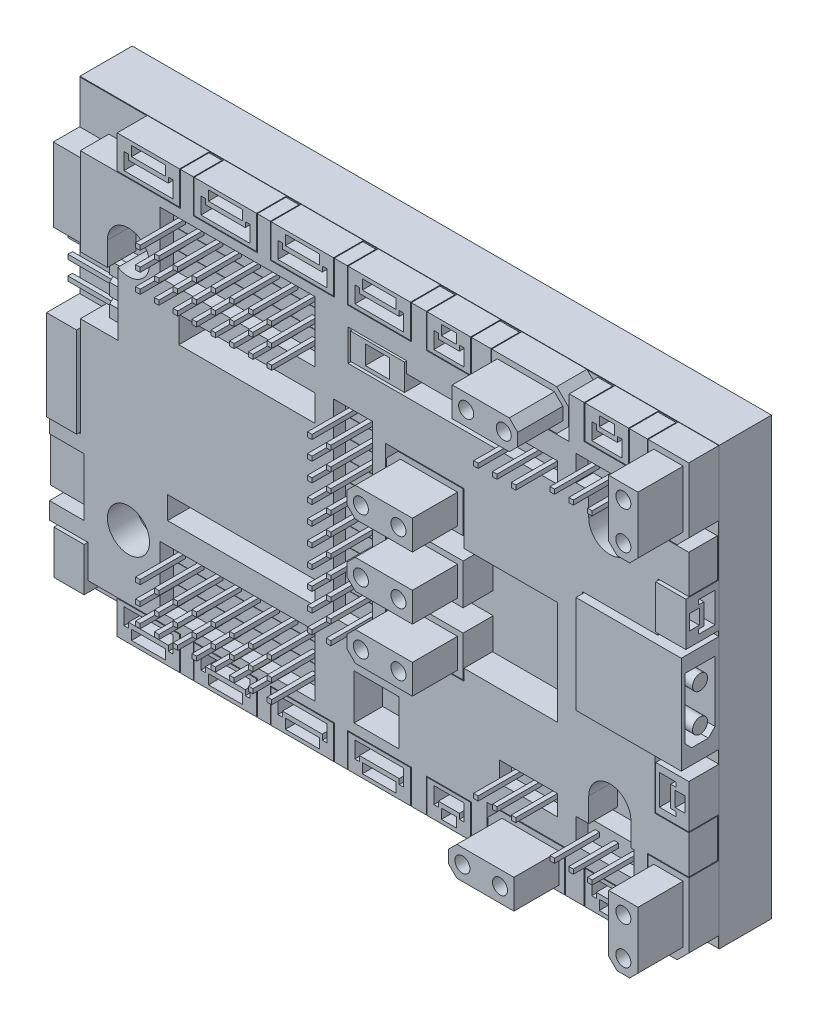
SolidWorks part; units mm, degrees
ref_plane "前视基准面" through (0, 0, 0) normal (0, 0, 1) x (1, 0, 0)
ref_plane "上视基准面" through (0, 0, 0) normal (0, 1, 0) x (1, 0, 0)
ref_plane "右视基准面" through (0, 0, 0) normal (1, 0, 0) x (0, 0, -1)
sketch "草图1" plane through (0, 0, 0) normal (0, 0, 1) x (1, 0, 0)
  line L0 (42.5, 58) -> (42.5, 0) construction
  line L1 (0, 0) -> (85, 0)
  line L2 (0, 0) -> (0, 58)
  line L3 (0, 58) -> (85, 58)
  line L4 (85, 0) -> (85, 58)
  line L5 (74.5, 13) -> (10.5, 13) construction
  line L6 (74.5, 13) -> (74.5, 45) construction
  line L7 (74.5, 45) -> (10.5, 45) construction
  line L8 (10.5, 13) -> (10.5, 45) construction
  line L9 (74.5, 13) -> (10.5, 45) construction
  line L10 (74.5, 45) -> (10.5, 13) construction
  circle A0 centre (10.5, 45) radius 1.6
  circle A1 centre (10.5, 13) radius 1.6
  circle A2 centre (74.5, 45) radius 1.6
  circle A3 centre (74.5, 13) radius 1.6
  point P5 (42.5, 29)
  dimension "D5" = 3.2
  dimension "D1" = 85
  dimension "D2" = 58
  dimension "D3" = 32
  dimension "D4" = 64
extrude "板厚" add sketch "草图1" along normal blind 7
sketch "草图22" plane through (0, 0, 7) normal (0, 0, 1) x (1, 0, 0)
  line L0 (0.05, 57.95) -> (0.05, 0.05)
  line L1 (0.05, 0.05) -> (84.95, 0.05)
  line L2 (84.95, 0.05) -> (84.95, 57.95)
  line L3 (84.95, 57.95) -> (0.05, 57.95)
  line L4 (0, 58) -> (0, 0)
  line L5 (0, 0) -> (85, 0)
  line L6 (85, 0) -> (85, 58)
  line L7 (85, 58) -> (0, 58)
  line L8 (0, 58) -> (0, 0)
  line L9 (0, 0) -> (85, 0)
  line L10 (85, 0) -> (85, 58)
  line L11 (85, 58) -> (0, 58)
  dimension "D1" = 0
  dimension "D2" = 0.05
extrude "切除-拉伸6" cut sketch "草图22" against normal blind 0.05
sketch "草图2" plane through (85, 0, 0) normal (1, 0, 0) x (0, 0, -1)
  line L0 (-7, 0) -> (-7, 58) construction
  line L1 (-7, 23) -> (-12, 23)
  line L2 (-7, 23) -> (-7, 36)
  line L3 (-7, 36) -> (-12, 36)
  line L4 (-12, 23) -> (-12, 36)
  line L5 (-6.95, 58) -> (0, 58) construction
  line L6 (-10.6, 25) -> (-11.5, 25.9)
  line L7 (-11.5, 25.9) -> (-11.5, 34)
  line L8 (-11.5, 34) -> (-7.5, 34)
  line L9 (-7.5, 34) -> (-7.5, 25.9)
  line L10 (-7.5, 25.9) -> (-8.4, 25)
  line L11 (-8.4, 25) -> (-10.6, 25)
  line L12 (-9.5, 23) -> (-9.5, 27) construction
  line L13 (-9.5, 27) -> (-9.5, 32) construction
  line L14 (-9.5, 32) -> (-9.5, 36) construction
  circle A0 centre (-9.5, 27) radius 1
  circle A1 centre (-9.5, 32) radius 1
  dimension "D12" = 2
  dimension "D1" = 22
  dimension "D2" = 13
  dimension "D3" = 5
  dimension "D4" = 45
  dimension "D5" = 45
  dimension "D6" = 2
  dimension "D7" = 0.5
  dimension "D8" = 0.5
  dimension "D9" = 2
  dimension "D10" = 2.2
  dimension "D11" = 5
extrude "xt30侧向" add sketch "草图2" against normal blind 14 contours A0 | A1 | L4 L1 L3 L10 L11 L6 L7 L8 L9 region at (85, 23.1393, 9.5) region at (85, 27, 9.5) region at (85, 32, 9.5)
sketch "草图3" plane through (85, 0, 0) normal (1, 0, 0) x (0, 0, -1)
  line L0 (-7, 36) -> (-7, 58) construction
  line L1 (-7, 36.7) -> (-11.4, 36.7)
  line L2 (-7, 36.7) -> (-7, 42.5)
  line L3 (-7, 42.5) -> (-11.4, 42.5)
  line L4 (-11.4, 36.7) -> (-11.4, 42.5)
  line L5 (-6.95, 58) -> (0, 58) construction
  line L6 (-10.9, 39.6) -> (-11.4, 39.6) construction
  line L7 (-10.9, 38.6) -> (-9.6, 38.6)
  line L8 (-10.9, 38.6) -> (-10.9, 40.6)
  line L9 (-10.9, 40.6) -> (-9.6, 40.6)
  line L10 (-9.6, 38.6) -> (-9.6, 40.6)
  line L11 (-9.7, 38.2) -> (-9, 38.2)
  line L12 (-9, 38.2) -> (-9, 41)
  line L13 (-9, 41) -> (-9.7, 41)
  line L14 (-9.7, 41) -> (-9.7, 41.6)
  line L15 (-9.7, 41.6) -> (-7.5, 41.6)
  line L16 (-7.5, 41.6) -> (-7.5, 37.6)
  line L17 (-7.5, 37.6) -> (-9.7, 37.6)
  line L18 (-9.7, 37.6) -> (-9.7, 38.2)
  line L19 (-9.6, 39.6) -> (-9, 39.6) construction
  dimension "D1" = 15.5
  dimension "D2" = 5.8
  dimension "D3" = 4.4
  dimension "D4" = 0.5
  dimension "D5" = 1.3
  dimension "D6" = 2
  dimension "D7" = 1.5
  dimension "D8" = 4
  dimension "D9" = 2.2
  dimension "D10" = 2.8
  dimension "D11" = 0.5
extrude "2pin CAN1侧向" add sketch "草图3" against normal blind 4
sketch "草图4" plane through (0, 0, 7) normal (0, 0, 1) x (1, 0, 0)
  line L0 (59.85, 0) -> (68.5, 0)
  line L1 (0, 0) -> (85, 0) construction
  line L2 (68.5, 0) -> (68.5, 5.4)
  line L3 (68.5, 5.4) -> (59.85, 5.4)
  line L4 (59.85, 5.4) -> (58.3, 3.85)
  line L5 (58.3, 3.85) -> (58.3, 1.55)
  line L6 (58.3, 1.55) -> (59.85, 0)
  line L7 (85, 0) -> (85, 23) construction
  line L8 (58.3, 2.7) -> (60.9, 2.7) construction
  line L9 (60.9, 2.7) -> (65.9, 2.7) construction
  line L10 (65.9, 2.7) -> (68.5, 2.7) construction
  line L11 (85, 1.55) -> (85, 10.2)
  line L12 (85, 10.2) -> (79.6, 10.2)
  line L13 (79.6, 10.2) -> (79.6, 1.55)
  line L14 (79.6, 1.55) -> (81.15, 0)
  line L15 (81.15, 0) -> (83.45, 0)
  line L16 (83.45, 0) -> (85, 1.55)
  line L17 (82.3, 0) -> (82.3, 2.6) construction
  line L18 (82.3, 2.6) -> (82.3, 7.6) construction
  line L19 (82.3, 7.6) -> (82.3, 10.2) construction
  line L20 (85, 49.35) -> (85, 58)
  line L21 (85, 58) -> (79.6, 58)
  line L22 (79.6, 58) -> (79.6, 49.35)
  line L23 (79.6, 49.35) -> (81.15, 47.8)
  line L24 (81.15, 47.8) -> (83.45, 47.8)
  line L25 (83.45, 47.8) -> (85, 49.35)
  line L26 (82.3, 47.8) -> (82.3, 50.4) construction
  line L27 (82.3, 50.4) -> (82.3, 55.4) construction
  line L28 (82.3, 55.4) -> (82.3, 58) construction
  line L29 (67.45, 58) -> (58.8, 58)
  line L30 (58.8, 58) -> (58.8, 52.6)
  line L31 (58.8, 52.6) -> (67.45, 52.6)
  line L32 (67.45, 52.6) -> (69, 54.15)
  line L33 (69, 54.15) -> (69, 56.45)
  line L34 (69, 56.45) -> (67.45, 58)
  line L35 (69, 55.3) -> (66.4, 55.3) construction
  line L36 (66.4, 55.3) -> (61.4, 55.3) construction
  line L37 (61.4, 55.3) -> (58.8, 55.3) construction
  line L38 (85, 58) -> (0, 58) construction
  line L39 (46.35, 34.6) -> (55, 34.6)
  line L40 (55, 34.6) -> (55, 40)
  line L41 (55, 40) -> (46.35, 40)
  line L42 (46.35, 40) -> (44.8, 38.45)
  line L43 (44.8, 38.45) -> (44.8, 36.15)
  line L44 (44.8, 36.15) -> (46.35, 34.6)
  line L45 (44.8, 37.3) -> (47.4, 37.3) construction
  line L46 (47.4, 37.3) -> (52.4, 37.3) construction
  line L47 (52.4, 37.3) -> (55, 37.3) construction
  line L48 (46.35, 26.3) -> (55, 26.3)
  line L49 (55, 26.3) -> (55, 31.7)
  line L50 (55, 31.7) -> (46.35, 31.7)
  line L51 (46.35, 31.7) -> (44.8, 30.15)
  line L52 (44.8, 30.15) -> (44.8, 27.85)
  line L53 (44.8, 27.85) -> (46.35, 26.3)
  line L54 (44.8, 29) -> (47.4, 29) construction
  line L55 (47.4, 29) -> (52.4, 29) construction
  line L56 (52.4, 29) -> (55, 29) construction
  line L57 (46.35, 18) -> (55, 18)
  line L58 (55, 18) -> (55, 23.4)
  line L59 (55, 23.4) -> (46.35, 23.4)
  line L60 (46.35, 23.4) -> (44.8, 21.85)
  line L61 (44.8, 21.85) -> (44.8, 19.55)
  line L62 (44.8, 19.55) -> (46.35, 18)
  line L63 (44.8, 20.7) -> (47.4, 20.7) construction
  line L64 (47.4, 20.7) -> (52.4, 20.7) construction
  line L65 (52.4, 20.7) -> (55, 20.7) construction
  circle A0 centre (60.9, 2.7) radius 1
  circle A1 centre (65.9, 2.7) radius 1
  circle A2 centre (82.3, 2.6) radius 1
  circle A3 centre (82.3, 7.6) radius 1
  circle A4 centre (82.3, 50.4) radius 1
  circle A5 centre (82.3, 55.4) radius 1
  circle A6 centre (66.4, 55.3) radius 1
  circle A7 centre (61.4, 55.3) radius 1
  circle A8 centre (47.4, 37.3) radius 1
  circle A9 centre (52.4, 37.3) radius 1
  circle A10 centre (47.4, 29) radius 1
  circle A11 centre (52.4, 29) radius 1
  circle A12 centre (47.4, 20.7) radius 1
  circle A13 centre (52.4, 20.7) radius 1
  dimension "D8" = 2
  dimension "D15" = 2
  dimension "D22" = 2
  dimension "D29" = 2
  dimension "D37" = 2
  dimension "D1" = 5.4
  dimension "D2" = 45
  dimension "D3" = 45
  dimension "D4" = 10.2
  dimension "D5" = 16.5
  dimension "D6" = 2.3
  dimension "D7" = 5
  dimension "D9" = 5.4
  dimension "D10" = 45
  dimension "D11" = 45
  dimension "D12" = 10.2
  dimension "D13" = 2.3
  dimension "D14" = 5
  dimension "D16" = 5.4
  dimension "D17" = 45
  dimension "D18" = 45
  dimension "D19" = 10.2
  dimension "D20" = 2.3
  dimension "D21" = 5
  dimension "D23" = 5.4
  dimension "D24" = 45
  dimension "D25" = 45
  dimension "D26" = 10.2
  dimension "D27" = 2.3
  dimension "D28" = 5
  dimension "D30" = 16
  dimension "D31" = 5.4
  dimension "D32" = 45
  dimension "D33" = 45
  dimension "D34" = 10.2
  dimension "D35" = 2.3
  dimension "D36" = 5
  dimension "D38" = 40
  dimension "D39" = 30
  dimension "D41" = 22
  dimension "D40" = 3
extrude "xt30法向" add sketch "草图4" along normal blind 10
sketch "草图20" plane through (0, 0, 7) normal (0, 0, 1) x (1, 0, 0)
  line L0 (40, 47.2) -> (40, 50.7)
  line L1 (40, 50.7) -> (47.2, 50.7)
  line L2 (47.2, 50.7) -> (47.2, 47.2)
  line L3 (47.2, 47.2) -> (40, 47.2)
  line L4 (42, 50.2) -> (45.2, 50.2)
  line L5 (45.2, 50.2) -> (45.2, 47.7)
  line L6 (45.2, 47.7) -> (42, 47.7)
  line L7 (42, 47.7) -> (42, 50.2)
  line L8 (43.6, 50.7) -> (43.6, 50.2) construction
  line L9 (58.8, 58) -> (0, 58) construction
  line L10 (85, 42.5) -> (85, 49.35) construction
  dimension "D1" = 7.2
  dimension "D2" = 3.5
  dimension "D3" = 3.2
  dimension "D4" = 0.5
  dimension "D5" = 0.5
  dimension "D6" = 10.8
  dimension "D7" = 45
extrude "2pin法向" add sketch "草图20" along normal blind 4
sketch "草图5" plane through (0, 0, 7) normal (0, 0, 1) x (1, 0, 0)
  line L0 (56, 4.4) -> (56, 0)
  line L1 (56, 4.4) -> (50.2, 4.4)
  line L2 (50.2, 4.4) -> (50.2, 0)
  line L3 (56, 0) -> (50.2, 0)
  line L4 (53.1, 0.5) -> (53.1, 0) construction
  line L5 (54.1, 0.5) -> (54.1, 1.8)
  line L6 (54.1, 0.5) -> (52.1, 0.5)
  line L7 (52.1, 0.5) -> (52.1, 1.8)
  line L8 (54.1, 1.8) -> (52.1, 1.8)
  line L9 (54.5, 1.7) -> (54.5, 2.4)
  line L10 (54.5, 2.4) -> (51.7, 2.4)
  line L11 (51.7, 2.4) -> (51.7, 1.7)
  line L12 (51.7, 1.7) -> (51.1, 1.7)
  line L13 (51.1, 1.7) -> (51.1, 3.9)
  line L14 (51.1, 3.9) -> (55.1, 3.9)
  line L15 (55.1, 3.9) -> (55.1, 1.7)
  line L16 (55.1, 1.7) -> (54.5, 1.7)
  line L17 (53.1, 1.8) -> (53.1, 2.4) construction
  line L18 (0, 0) -> (59.85, 0) construction
  line L19 (85, 0) -> (85, 1.55) construction
  line L20 (77, 4.4) -> (77, 0)
  line L21 (77, 4.4) -> (71.2, 4.4)
  line L22 (71.2, 4.4) -> (71.2, 0)
  line L23 (77, 0) -> (71.2, 0)
  line L24 (74.1, 0.5) -> (74.1, 0) construction
  line L25 (75.1, 0.5) -> (75.1, 1.8)
  line L26 (75.1, 0.5) -> (73.1, 0.5)
  line L27 (73.1, 0.5) -> (73.1, 1.8)
  line L28 (75.1, 1.8) -> (73.1, 1.8)
  line L29 (75.5, 1.7) -> (75.5, 2.4)
  line L30 (75.5, 2.4) -> (72.7, 2.4)
  line L31 (72.7, 2.4) -> (72.7, 1.7)
  line L32 (72.7, 1.7) -> (72.1, 1.7)
  line L33 (72.1, 1.7) -> (72.1, 3.9)
  line L34 (72.1, 3.9) -> (76.1, 3.9)
  line L35 (76.1, 3.9) -> (76.1, 1.7)
  line L36 (76.1, 1.7) -> (75.5, 1.7)
  line L37 (74.1, 1.8) -> (74.1, 2.4) construction
  line L38 (68.5, 0) -> (81.15, 0) construction
  line L39 (80.6, 21.3) -> (85, 21.3)
  line L40 (80.6, 21.3) -> (80.6, 15.5)
  line L41 (80.6, 15.5) -> (85, 15.5)
  line L42 (85, 21.3) -> (85, 15.5)
  line L43 (84.5, 18.4) -> (85, 18.4) construction
  line L44 (84.5, 19.4) -> (83.2, 19.4)
  line L45 (84.5, 19.4) -> (84.5, 17.4)
  line L46 (84.5, 17.4) -> (83.2, 17.4)
  line L47 (83.2, 19.4) -> (83.2, 17.4)
  line L48 (83.3, 19.8) -> (82.6, 19.8)
  line L49 (82.6, 19.8) -> (82.6, 17)
  line L50 (82.6, 17) -> (83.3, 17)
  line L51 (83.3, 17) -> (83.3, 16.4)
  line L52 (83.3, 16.4) -> (81.1, 16.4)
  line L53 (81.1, 16.4) -> (81.1, 20.4)
  line L54 (81.1, 20.4) -> (83.3, 20.4)
  line L55 (83.3, 20.4) -> (83.3, 19.8)
  line L56 (83.2, 18.4) -> (82.6, 18.4) construction
  line L57 (85, 10.2) -> (85, 23) construction
  line L58 (83.45, 0) -> (85, 0) construction
  line L63 (71.2, 53.6) -> (71.2, 58)
  line L76 (71.2, 53.6) -> (77, 53.6)
  line L77 (77, 53.6) -> (77, 58)
  line L78 (71.2, 58) -> (77, 58)
  line L79 (74.1, 57.5) -> (74.1, 58) construction
  line L80 (73.1, 57.5) -> (73.1, 56.2)
  line L81 (73.1, 57.5) -> (75.1, 57.5)
  line L82 (75.1, 57.5) -> (75.1, 56.2)
  line L83 (73.1, 56.2) -> (75.1, 56.2)
  line L84 (72.7, 56.3) -> (72.7, 55.6)
  line L85 (72.7, 55.6) -> (75.5, 55.6)
  line L86 (75.5, 55.6) -> (75.5, 56.3)
  line L87 (75.5, 56.3) -> (76.1, 56.3)
  line L88 (76.1, 56.3) -> (76.1, 54.1)
  line L89 (76.1, 54.1) -> (72.1, 54.1)
  line L90 (72.1, 54.1) -> (72.1, 56.3)
  line L91 (72.1, 56.3) -> (72.7, 56.3)
  line L92 (74.1, 56.2) -> (74.1, 55.6) construction
  line L93 (79.6, 58) -> (67.45, 58) construction
  line L94 (85, 42.5) -> (85, 49.35) construction
  line L95 (50.2, 53.6) -> (50.2, 58)
  line L96 (50.2, 53.6) -> (56, 53.6)
  line L97 (56, 53.6) -> (56, 58)
  line L98 (50.2, 58) -> (56, 58)
  line L99 (53.1, 57.5) -> (53.1, 58) construction
  line L100 (52.1, 57.5) -> (52.1, 56.2)
  line L101 (52.1, 57.5) -> (54.1, 57.5)
  line L102 (54.1, 57.5) -> (54.1, 56.2)
  line L103 (52.1, 56.2) -> (54.1, 56.2)
  line L104 (51.7, 56.3) -> (51.7, 55.6)
  line L105 (51.7, 55.6) -> (54.5, 55.6)
  line L106 (54.5, 55.6) -> (54.5, 56.3)
  line L107 (54.5, 56.3) -> (55.1, 56.3)
  line L108 (55.1, 56.3) -> (55.1, 54.1)
  line L109 (55.1, 54.1) -> (51.1, 54.1)
  line L110 (51.1, 54.1) -> (51.1, 56.3)
  line L111 (51.1, 56.3) -> (51.7, 56.3)
  line L112 (53.1, 56.2) -> (53.1, 55.6) construction
  line L113 (58.8, 58) -> (0, 58) construction
  dimension "D1" = 5.8
  dimension "D2" = 4.4
  dimension "D3" = 0.5
  dimension "D4" = 1.3
  dimension "D5" = 2
  dimension "D6" = 1.5
  dimension "D7" = 4
  dimension "D8" = 2.2
  dimension "D9" = 2.8
  dimension "D10" = 0.5
  dimension "D11" = 29
  dimension "D12" = 5.8
  dimension "D13" = 4.4
  dimension "D14" = 0.5
  dimension "D15" = 1.3
  dimension "D16" = 2
  dimension "D17" = 1.5
  dimension "D18" = 4
  dimension "D19" = 2.2
  dimension "D20" = 2.8
  dimension "D21" = 0.5
  dimension "D22" = 8
  dimension "D23" = 5.8
  dimension "D24" = 4.4
  dimension "D25" = 0.5
  dimension "D26" = 1.3
  dimension "D27" = 2
  dimension "D28" = 1.5
  dimension "D29" = 4
  dimension "D30" = 2.2
  dimension "D31" = 2.8
  dimension "D32" = 0.5
  dimension "D33" = 15.5
  dimension "D34" = 5.8
  dimension "D35" = 4.4
  dimension "D36" = 0.5
  dimension "D37" = 1.3
  dimension "D38" = 2
  dimension "D39" = 1.5
  dimension "D40" = 4
  dimension "D41" = 2.2
  dimension "D42" = 2.8
  dimension "D43" = 0.5
  dimension "D44" = 8
  dimension "D45" = 5.8
  dimension "D46" = 4.4
  dimension "D47" = 0.5
  dimension "D48" = 1.3
  dimension "D49" = 2
  dimension "D50" = 1.5
  dimension "D51" = 4
  dimension "D52" = 2.2
  dimension "D53" = 2.8
  dimension "D54" = 0.5
  dimension "D55" = 29
extrude "2pin CAN1" add sketch "草图5" along normal blind 4
sketch "草图6" plane through (0, 0, 7) normal (0, 0, 1) x (1, 0, 0)
  line L0 (9, 53.6) -> (9, 58)
  line L1 (9, 53.6) -> (17.3, 53.6)
  line L2 (17.3, 53.6) -> (17.3, 58)
  line L3 (9, 58) -> (17.3, 58)
  line L4 (13.15, 57.5) -> (13.15, 58) construction
  line L5 (10.9, 57.5) -> (10.9, 56.2)
  line L6 (10.9, 57.5) -> (15.4, 57.5)
  line L7 (15.4, 57.5) -> (15.4, 56.2)
  line L8 (10.9, 56.2) -> (15.4, 56.2)
  line L9 (10.5, 56.3) -> (10.5, 55.6)
  line L10 (10.5, 55.6) -> (15.8, 55.6)
  line L11 (15.8, 55.6) -> (15.8, 56.3)
  line L12 (15.8, 56.3) -> (16.4, 56.3)
  line L13 (16.4, 56.3) -> (16.4, 54.1)
  line L14 (16.4, 54.1) -> (9.9, 54.1)
  line L15 (9.9, 54.1) -> (9.9, 56.3)
  line L16 (9.9, 56.3) -> (10.5, 56.3)
  line L17 (13.15, 56.2) -> (13.15, 55.6) construction
  line L18 (50.2, 58) -> (0, 58) construction
  line L19 (85, 42.5) -> (85, 49.35) construction
  line L20 (19.2333, 53.6) -> (19.2333, 58)
  line L21 (19.2333, 53.6) -> (27.5333, 53.6)
  line L22 (27.5333, 53.6) -> (27.5333, 58)
  line L23 (19.2333, 58) -> (27.5333, 58)
  line L24 (21.1333, 57.5) -> (21.1333, 56.2)
  line L25 (21.1333, 57.5) -> (25.6333, 57.5)
  line L26 (25.6333, 57.5) -> (25.6333, 56.2)
  line L27 (21.1333, 56.2) -> (25.6333, 56.2)
  line L28 (20.7333, 56.3) -> (20.7333, 55.6)
  line L29 (20.7333, 55.6) -> (26.0333, 55.6)
  line L30 (26.0333, 55.6) -> (26.0333, 56.3)
  line L31 (26.0333, 56.3) -> (26.6333, 56.3)
  line L32 (26.6333, 56.3) -> (26.6333, 54.1)
  line L33 (26.6333, 54.1) -> (20.1333, 54.1)
  line L34 (20.1333, 54.1) -> (20.1333, 56.3)
  line L35 (20.1333, 56.3) -> (20.7333, 56.3)
  line L36 (23.3833, 57.5) -> (23.3833, 58) construction
  line L37 (23.3833, 56.2) -> (23.3833, 55.6) construction
  line L38 (29.4667, 53.6) -> (29.4667, 58)
  line L39 (29.4667, 53.6) -> (37.7667, 53.6)
  line L40 (37.7667, 53.6) -> (37.7667, 58)
  line L41 (29.4667, 58) -> (37.7667, 58)
  line L42 (31.3667, 57.5) -> (31.3667, 56.2)
  line L43 (31.3667, 57.5) -> (35.8667, 57.5)
  line L44 (35.8667, 57.5) -> (35.8667, 56.2)
  line L45 (31.3667, 56.2) -> (35.8667, 56.2)
  line L46 (30.9667, 56.3) -> (30.9667, 55.6)
  line L47 (30.9667, 55.6) -> (36.2667, 55.6)
  line L48 (36.2667, 55.6) -> (36.2667, 56.3)
  line L49 (36.2667, 56.3) -> (36.8667, 56.3)
  line L50 (36.8667, 56.3) -> (36.8667, 54.1)
  line L51 (36.8667, 54.1) -> (30.3667, 54.1)
  line L52 (30.3667, 54.1) -> (30.3667, 56.3)
  line L53 (30.3667, 56.3) -> (30.9667, 56.3)
  line L54 (33.6167, 57.5) -> (33.6167, 58) construction
  line L55 (33.6167, 56.2) -> (33.6167, 55.6) construction
  line L56 (39.7, 53.6) -> (39.7, 58)
  line L57 (39.7, 53.6) -> (48, 53.6)
  line L58 (48, 53.6) -> (48, 58)
  line L59 (39.7, 58) -> (48, 58)
  line L60 (41.6, 57.5) -> (41.6, 56.2)
  line L61 (41.6, 57.5) -> (46.1, 57.5)
  line L62 (46.1, 57.5) -> (46.1, 56.2)
  line L63 (41.6, 56.2) -> (46.1, 56.2)
  line L64 (41.2, 56.3) -> (41.2, 55.6)
  line L65 (41.2, 55.6) -> (46.5, 55.6)
  line L66 (46.5, 55.6) -> (46.5, 56.3)
  line L67 (46.5, 56.3) -> (47.1, 56.3)
  line L68 (47.1, 56.3) -> (47.1, 54.1)
  line L69 (47.1, 54.1) -> (40.6, 54.1)
  line L70 (40.6, 54.1) -> (40.6, 56.3)
  line L71 (40.6, 56.3) -> (41.2, 56.3)
  line L72 (43.85, 57.5) -> (43.85, 58) construction
  line L73 (43.85, 56.2) -> (43.85, 55.6) construction
  dimension "D1" = 8.3
  dimension "D2" = 4.4
  dimension "D3" = 0.5
  dimension "D4" = 1.3
  dimension "D5" = 4.5
  dimension "D6" = 1.5
  dimension "D7" = 6.5
  dimension "D8" = 2.2
  dimension "D9" = 5.3
  dimension "D10" = 0.5
  dimension "D11" = 76
  dimension "D13" = 39
  dimension "D12" = 4
extrude "4pin UART" add sketch "草图6" along normal blind 4
sketch "草图7" plane through (0, 0, 7) normal (0, 0, 1) x (1, 0, 0)
  line L0 (17.3, 4.4) -> (17.3, 0)
  line L1 (17.3, 4.4) -> (9, 4.4)
  line L2 (9, 4.4) -> (9, 0)
  line L3 (17.3, 0) -> (9, 0)
  line L4 (13.15, 0.5) -> (13.15, 0) construction
  line L5 (15.4, 0.5) -> (15.4, 1.8)
  line L6 (15.4, 0.5) -> (10.9, 0.5)
  line L7 (10.9, 0.5) -> (10.9, 1.8)
  line L8 (15.4, 1.8) -> (10.9, 1.8)
  line L9 (15.8, 1.7) -> (15.8, 2.4)
  line L10 (15.8, 2.4) -> (10.5, 2.4)
  line L11 (10.5, 2.4) -> (10.5, 1.7)
  line L12 (10.5, 1.7) -> (9.9, 1.7)
  line L13 (9.9, 1.7) -> (9.9, 3.9)
  line L14 (9.9, 3.9) -> (16.4, 3.9)
  line L15 (16.4, 3.9) -> (16.4, 1.7)
  line L16 (16.4, 1.7) -> (15.8, 1.7)
  line L17 (13.15, 1.8) -> (13.15, 2.4) construction
  line L18 (0, 0) -> (50.2, 0) construction
  line L19 (85, 10.2) -> (85, 15.5) construction
  line L20 (27.5333, 4.4) -> (27.5333, 0)
  line L21 (27.5333, 4.4) -> (19.2333, 4.4)
  line L22 (19.2333, 4.4) -> (19.2333, 0)
  line L23 (27.5333, 0) -> (19.2333, 0)
  line L24 (25.6333, 0.5) -> (25.6333, 1.8)
  line L25 (25.6333, 0.5) -> (21.1333, 0.5)
  line L26 (21.1333, 0.5) -> (21.1333, 1.8)
  line L27 (25.6333, 1.8) -> (21.1333, 1.8)
  line L28 (26.0333, 1.7) -> (26.0333, 2.4)
  line L29 (26.0333, 2.4) -> (20.7333, 2.4)
  line L30 (20.7333, 2.4) -> (20.7333, 1.7)
  line L31 (20.7333, 1.7) -> (20.1333, 1.7)
  line L32 (20.1333, 1.7) -> (20.1333, 3.9)
  line L33 (20.1333, 3.9) -> (26.6333, 3.9)
  line L34 (26.6333, 3.9) -> (26.6333, 1.7)
  line L35 (26.6333, 1.7) -> (26.0333, 1.7)
  line L36 (23.3833, 0.5) -> (23.3833, 0) construction
  line L37 (23.3833, 1.8) -> (23.3833, 2.4) construction
  line L38 (37.7667, 4.4) -> (37.7667, 0)
  line L39 (37.7667, 4.4) -> (29.4667, 4.4)
  line L40 (29.4667, 4.4) -> (29.4667, 0)
  line L41 (37.7667, 0) -> (29.4667, 0)
  line L42 (35.8667, 0.5) -> (35.8667, 1.8)
  line L43 (35.8667, 0.5) -> (31.3667, 0.5)
  line L44 (31.3667, 0.5) -> (31.3667, 1.8)
  line L45 (35.8667, 1.8) -> (31.3667, 1.8)
  line L46 (36.2667, 1.7) -> (36.2667, 2.4)
  line L47 (36.2667, 2.4) -> (30.9667, 2.4)
  line L48 (30.9667, 2.4) -> (30.9667, 1.7)
  line L49 (30.9667, 1.7) -> (30.3667, 1.7)
  line L50 (30.3667, 1.7) -> (30.3667, 3.9)
  line L51 (30.3667, 3.9) -> (36.8667, 3.9)
  line L52 (36.8667, 3.9) -> (36.8667, 1.7)
  line L53 (36.8667, 1.7) -> (36.2667, 1.7)
  line L54 (33.6167, 0.5) -> (33.6167, 0) construction
  line L55 (33.6167, 1.8) -> (33.6167, 2.4) construction
  line L56 (48, 4.4) -> (48, 0)
  line L57 (48, 4.4) -> (39.7, 4.4)
  line L58 (39.7, 4.4) -> (39.7, 0)
  line L59 (48, 0) -> (39.7, 0)
  line L60 (46.1, 0.5) -> (46.1, 1.8)
  line L61 (46.1, 0.5) -> (41.6, 0.5)
  line L62 (41.6, 0.5) -> (41.6, 1.8)
  line L63 (46.1, 1.8) -> (41.6, 1.8)
  line L64 (46.5, 1.7) -> (46.5, 2.4)
  line L65 (46.5, 2.4) -> (41.2, 2.4)
  line L66 (41.2, 2.4) -> (41.2, 1.7)
  line L67 (41.2, 1.7) -> (40.6, 1.7)
  line L68 (40.6, 1.7) -> (40.6, 3.9)
  line L69 (40.6, 3.9) -> (47.1, 3.9)
  line L70 (47.1, 3.9) -> (47.1, 1.7)
  line L71 (47.1, 1.7) -> (46.5, 1.7)
  line L72 (43.85, 0.5) -> (43.85, 0) construction
  line L73 (43.85, 1.8) -> (43.85, 2.4) construction
  dimension "D1" = 8.3
  dimension "D2" = 4.4
  dimension "D3" = 0.5
  dimension "D4" = 1.3
  dimension "D5" = 4.5
  dimension "D6" = 1.5
  dimension "D7" = 6.5
  dimension "D8" = 2.2
  dimension "D9" = 5.3
  dimension "D10" = 0.5
  dimension "D11" = 76
  dimension "D13" = 39
  dimension "D12" = 4
extrude "4pin CAN2" add sketch "草图7" along normal blind 4
sketch "草图9" plane through (0, 0, 0) normal (-1, 0, 0) x (0, 0, 1)
  line L0 (7, 8.8) -> (11.4, 8.8)
  line L1 (7, 8.8) -> (7, 3)
  line L2 (7, 3) -> (11.4, 3)
  line L3 (11.4, 8.8) -> (11.4, 3)
  line L4 (10.9, 5.9) -> (11.4, 5.9) construction
  line L5 (10.9, 6.9) -> (9.6, 6.9)
  line L6 (10.9, 6.9) -> (10.9, 4.9)
  line L7 (10.9, 4.9) -> (9.6, 4.9)
  line L8 (9.6, 6.9) -> (9.6, 4.9)
  line L9 (9.7, 7.3) -> (9, 7.3)
  line L10 (9, 7.3) -> (9, 4.5)
  line L11 (9, 4.5) -> (9.7, 4.5)
  line L12 (9.7, 4.5) -> (9.7, 3.9)
  line L13 (9.7, 3.9) -> (7.5, 3.9)
  line L14 (7.5, 3.9) -> (7.5, 7.9)
  line L15 (7.5, 7.9) -> (9.7, 7.9)
  line L16 (9.7, 7.9) -> (9.7, 7.3)
  line L17 (9.6, 5.9) -> (9, 5.9) construction
  line L18 (7, 10.2) -> (7, 1.55) construction
  line L19 (6.95, 0) -> (0, 0) construction
  dimension "D1" = 5.8
  dimension "D2" = 4.4
  dimension "D3" = 0.5
  dimension "D4" = 1.3
  dimension "D5" = 2
  dimension "D6" = 1.5
  dimension "D7" = 4
  dimension "D8" = 2.2
  dimension "D9" = 2.8
  dimension "D10" = 0.5
  dimension "D11" = 3
extrude "2pin" add sketch "草图9" against normal blind 4 from offset 1 offset against normal yes
sketch "草图10" plane through (0, 0, 0) normal (-1, 0, 0) x (0, 0, 1)
  line L0 (7, 17.45) -> (7, 12.55)
  line L1 (7, 12.55) -> (8.3, 11.25)
  line L2 (8.3, 11.25) -> (9.2373, 11.25)
  line L3 (9.2373, 11.25) -> (9.9, 11.9127)
  line L4 (9.9, 11.9127) -> (9.9, 18.0873)
  line L5 (9.9, 18.0873) -> (9.2373, 18.75)
  line L6 (9.2373, 18.75) -> (8.3, 18.75)
  line L7 (8.3, 18.75) -> (7, 17.45)
  line L8 (7, 58) -> (7, 0) construction
  line L9 (6.95, 0) -> (0, 0) construction
  line L10 (8.4657, 18.35) -> (7.4, 17.2843)
  line L11 (7.4, 17.2843) -> (7.4, 12.7157)
  line L12 (7.4, 12.7157) -> (8.4657, 11.65)
  line L13 (8.4657, 11.65) -> (9.0716, 11.65)
  line L14 (9.0716, 11.65) -> (9.5, 12.0784)
  line L15 (9.5, 12.0784) -> (9.5, 17.9216)
  line L16 (9.5, 17.9216) -> (9.0716, 18.35)
  line L17 (9.0716, 18.35) -> (8.4657, 18.35)
  point P14 (7, 15)
  dimension "D1" = 7.5
  dimension "D2" = 2.9
  dimension "D3" = 45
  dimension "D4" = 1.6
  dimension "D5" = 15
  dimension "D6" = 0.4
extrude "micro usb" add sketch "草图10" against normal blind 5.5 from offset 1 separate body
sketch "草图11" plane through (0, 0, 0) normal (-1, 0, 0) x (0, 0, 1)
  line L0 (7, 33) -> (11.4, 33)
  line L1 (7, 33) -> (7, 21)
  line L2 (7, 21) -> (11.4, 21)
  line L3 (11.4, 33) -> (11.4, 21)
  line L4 (10.9, 27) -> (11.4, 27) construction
  line L5 (10.9, 31.1) -> (9.6, 31.1)
  line L6 (10.9, 31.1) -> (10.9, 22.9)
  line L7 (10.9, 22.9) -> (9.6, 22.9)
  line L8 (9.6, 31.1) -> (9.6, 22.9)
  line L9 (9.7, 31.5) -> (9, 31.5)
  line L10 (9, 31.5) -> (9, 22.5)
  line L11 (9, 22.5) -> (9.7, 22.5)
  line L12 (9.7, 22.5) -> (9.7, 21.9)
  line L13 (9.7, 21.9) -> (7.5, 21.9)
  line L14 (7.5, 21.9) -> (7.5, 32.1)
  line L15 (7.5, 32.1) -> (9.7, 32.1)
  line L16 (9.7, 32.1) -> (9.7, 31.5)
  line L17 (9.6, 27) -> (9, 27) construction
  line L18 (7, 58) -> (7, 0) construction
  line L19 (6.95, 0) -> (0, 0) construction
  dimension "D1" = 12
  dimension "D2" = 4.4
  dimension "D3" = 0.5
  dimension "D4" = 1.3
  dimension "D5" = 8.2
  dimension "D6" = 1.5
  dimension "D7" = 10.2
  dimension "D8" = 2.2
  dimension "D9" = 9
  dimension "D10" = 0.5
  dimension "D11" = 21
extrude "7pin" add sketch "草图11" against normal blind 4
sketch "草图12" plane through (0, 0, 0) normal (-1, 0, 0) x (0, 0, 1)
  line L0 (7, 41.3) -> (7.45, 41.75)
  line L1 (7.45, 41.75) -> (9.05, 41.75)
  line L2 (9.05, 41.75) -> (9.5, 41.3)
  line L3 (9.5, 41.3) -> (9.5, 39.7)
  line L4 (9.5, 39.7) -> (9.05, 39.25)
  line L5 (9.05, 39.25) -> (9.5, 38.8)
  line L6 (9.5, 38.8) -> (9.5, 37.2)
  line L7 (9.5, 37.2) -> (9.05, 36.75)
  line L8 (9.05, 36.75) -> (9.5, 36.3)
  line L9 (9.5, 36.3) -> (9.5, 34.7)
  line L10 (9.5, 34.7) -> (9.05, 34.25)
  line L11 (9.05, 34.25) -> (7.45, 34.25)
  line L12 (7.45, 34.25) -> (7, 34.7)
  line L13 (7, 34.7) -> (7, 36.3)
  line L14 (7, 36.3) -> (7.45, 36.75)
  line L15 (7.45, 36.75) -> (7, 37.2)
  line L16 (7, 37.2) -> (7, 38.8)
  line L17 (7, 38.8) -> (7.45, 39.25)
  line L18 (7.45, 39.25) -> (7, 39.7)
  line L19 (7, 39.7) -> (7, 41.3)
  line L20 (7, 58) -> (7, 33) construction
  line L21 (6.95, 0) -> (0, 0) construction
  point P24 (7, 38)
  dimension "D1" = 45
  dimension "D2" = 7.5
  dimension "D3" = 38
  dimension "D4" = 2.5
  dimension "D5" = 1.6
extrude "遥控器接收端插口A" add sketch "草图12" against normal blind 9
sketch "草图13" plane through (0, 0, 0) normal (-1, 0, 0) x (0, 0, 1)
  line L0 (7, 58) -> (7, 41.3) construction
  line L1 (8.55, 40.8) -> (7.95, 40.8)
  line L2 (8.55, 40.8) -> (8.55, 40.2)
  line L3 (8.55, 40.2) -> (7.95, 40.2)
  line L4 (7.95, 40.8) -> (7.95, 40.2)
  line L5 (8.55, 38.3) -> (7.95, 38.3)
  line L6 (8.55, 38.3) -> (8.55, 37.7)
  line L7 (8.55, 37.7) -> (7.95, 37.7)
  line L8 (7.95, 38.3) -> (7.95, 37.7)
  line L9 (8.55, 35.8) -> (7.95, 35.8)
  line L10 (8.55, 35.8) -> (8.55, 35.2)
  line L11 (8.55, 35.2) -> (7.95, 35.2)
  line L12 (7.95, 35.8) -> (7.95, 35.2)
  line L13 (7, 41.75) -> (9.5, 41.75)
  line L14 (7, 41.75) -> (7, 34.25)
  line L15 (7, 34.25) -> (9.5, 34.25)
  line L16 (9.5, 41.75) -> (9.5, 34.25)
  line L17 (9.5, 34.7) -> (9.5, 36.3) construction
  line L18 (7.45, 34.25) -> (9.05, 34.25) construction
  line L19 (9.05, 41.75) -> (7.45, 41.75) construction
  line L20 (8.25, 41.75) -> (8.25, 40.8) construction
  line L21 (8.25, 40.8) -> (8.25, 40.2) construction
  line L22 (8.25, 40.2) -> (8.25, 38.3) construction
  line L23 (8.25, 38.3) -> (8.25, 37.7) construction
  line L24 (8.25, 37.7) -> (8.25, 35.8) construction
  line L25 (8.25, 35.8) -> (8.25, 35.2) construction
  line L26 (8.25, 35.2) -> (8.25, 34.25) construction
  point P32 (8.55, 40.5)
  point P33 (8.55, 35.5)
  dimension "D1" = 0.6
  dimension "D2" = 5
extrude "遥控器接收端插口" cut sketch "草图13" against normal blind 6.5
sketch "草图14" plane through (0, 0, 0) normal (-1, 0, 0) x (0, 0, 1)
  line L0 (7, 52.2) -> (10.5, 52.2)
  line L1 (7, 58) -> (7, 33) construction
  line L2 (10.5, 52.2) -> (10.5, 42.4)
  line L3 (10.5, 42.4) -> (7, 42.4)
  line L4 (7, 42.4) -> (7, 52.2)
  line L5 (10, 50.2) -> (10, 44.4)
  line L6 (10, 44.4) -> (7.5, 44.4)
  line L7 (7.5, 44.4) -> (7.5, 50.2)
  line L8 (7.5, 50.2) -> (10, 50.2)
  line L9 (10.5, 47.3) -> (10, 47.3) construction
  line L10 (6.95, 0) -> (0, 0) construction
  dimension "D1" = 9.8
  dimension "D2" = 3.5
  dimension "D3" = 5.8
  dimension "D4" = 0.5
  dimension "D5" = 0.5
  dimension "D6" = 52.2
extrude "4pin烧写口" add sketch "草图14" against normal blind 4
sketch "草图17" plane through (0, 0, 7) normal (0, 0, 1) x (1, 0, 0)
  line L0 (15, 51.55) -> (15.45, 52)
  line L1 (15.45, 52) -> (17.05, 52)
  line L2 (17.05, 52) -> (17.5, 51.55)
  line L3 (17.5, 51.55) -> (17.5, 50.0167)
  line L4 (17.5, 50.0167) -> (17.025, 49.5417)
  line L5 (17.025, 49.4917) -> (17.5, 49.0167)
  line L6 (17.5, 49.0167) -> (17.5, 47.4833)
  line L7 (17.5, 47.4833) -> (17.025, 47.0083)
  line L8 (17.025, 46.9583) -> (17.5, 46.4833)
  line L9 (17.5, 46.4833) -> (17.5, 44.95)
  line L10 (17.5, 44.95) -> (17.05, 44.5)
  line L11 (17.05, 44.5) -> (15.45, 44.5)
  line L12 (15.45, 44.5) -> (15, 44.95)
  line L13 (15, 44.95) -> (15, 46.4833)
  line L14 (15, 46.4833) -> (15.475, 46.9583)
  line L15 (15.475, 47.0083) -> (15, 47.4833)
  line L16 (15, 47.4833) -> (15, 49.0167)
  line L17 (15, 49.0167) -> (15.475, 49.4917)
  line L18 (15.475, 49.5417) -> (15, 50.0167)
  line L19 (15, 50.0167) -> (15, 51.55)
  line L20 (0, 50.7833) -> (15, 50.7833) construction
  line L21 (0, 58) -> (0, 52.2) construction
  line L22 (16.25, 58) -> (16.25, 52) construction
  line L23 (9, 58) -> (0, 58) construction
  line L24 (15.475, 49.5417) -> (17.025, 49.5417)
  line L25 (17.025, 49.5417) -> (17.025, 49.4917) construction
  line L26 (17.025, 49.4917) -> (15.475, 49.4917)
  line L27 (15.475, 49.4917) -> (15.475, 49.5417) construction
  line L28 (15.475, 47.0083) -> (17.025, 47.0083)
  line L29 (17.025, 47.0083) -> (17.025, 46.9583) construction
  line L30 (17.025, 46.9583) -> (15.475, 46.9583)
  line L31 (15.475, 46.9583) -> (15.475, 47.0083) construction
  dimension "D1" = 45
  dimension "D2" = 7.5
  dimension "D3" = 2.5
  dimension "D4" = 1.6
  dimension "D5" = 6
  dimension "D6" = 15
  dimension "D7" = 0.05
  dimension "D8" = 1
extrude "凸台-拉伸16" add sketch "草图17" along normal blind 8.5
sketch "草图18" plane through (0, 0, 15.5) normal (0, 0, 1) x (1, 0, 0)
  line L0 (16.25, 52) -> (16.25, 50.7833) construction
  line L1 (15.95, 50.4833) -> (16.55, 50.4833)
  line L2 (15.95, 50.4833) -> (15.95, 51.0833)
  line L3 (15.95, 51.0833) -> (16.55, 51.0833)
  line L4 (16.55, 50.4833) -> (16.55, 51.0833)
  line L5 (15.95, 50.4833) -> (16.55, 51.0833) construction
  line L6 (15.95, 51.0833) -> (16.55, 50.4833) construction
  line L7 (15.95, 48.55) -> (16.55, 48.55)
  line L8 (15.95, 48.55) -> (15.95, 47.95)
  line L9 (15.95, 47.95) -> (16.55, 47.95)
  line L10 (16.55, 48.55) -> (16.55, 47.95)
  line L11 (15.95, 48.55) -> (16.55, 47.95) construction
  line L12 (15.95, 47.95) -> (16.55, 48.55) construction
  line L13 (15.95, 45.4167) -> (16.55, 45.4167)
  line L14 (15.95, 45.4167) -> (15.95, 46.0167)
  line L15 (15.95, 46.0167) -> (16.55, 46.0167)
  line L16 (16.55, 45.4167) -> (16.55, 46.0167)
  line L17 (15.95, 45.4167) -> (16.55, 46.0167) construction
  line L18 (15.95, 46.0167) -> (16.55, 45.4167) construction
  line L19 (17.05, 52) -> (15.45, 52) construction
  line L20 (16.25, 50.7833) -> (16.25, 48.25) construction
  line L21 (16.25, 48.25) -> (16.25, 45.7167) construction
  line L22 (16.25, 45.7167) -> (16.25, 44.5) construction
  line L23 (15.45, 44.5) -> (17.05, 44.5) construction
  line L24 (16.25, 45.7167) -> (17.5, 45.7167) construction
  line L25 (17.5, 44.95) -> (17.5, 46.4833) construction
  line L26 (17.05, 52) -> (15.45, 52) construction
  line L27 (18.1, 43.9) -> (14.4, 43.9)
  line L28 (18.1, 43.9) -> (18.1, 52.6)
  line L29 (18.1, 52.6) -> (14.4, 52.6)
  line L30 (14.4, 43.9) -> (14.4, 52.6)
  line L31 (18.1, 43.9) -> (14.4, 52.6) construction
  line L32 (18.1, 52.6) -> (14.4, 43.9) construction
  line L33 (17.5, 47.4833) -> (17.5, 49.0167) construction
  point P0 (16.25, 50.7833)
  point P5 (16.25, 48.25)
  point P10 (16.25, 45.7167)
  dimension "D1" = 0.6
  dimension "D2" = 0.6
  dimension "D3" = 0.6
  dimension "D4" = 0.6
extrude "切除-拉伸4" cut sketch "草图18" against normal blind 6
pattern_linear "阵列(线性)1" count 8 spacing 2.5 along (1, 0, 0) of "凸台-拉伸16", "切除-拉伸4"
sketch "草图25" plane through (0, 0, 7) normal (0, 0, 1) x (1, 0, 0)
  line L0 (84.95, 42.5) -> (84.95, 49.3) construction
  line L1 (59.95, 49.4) -> (67.45, 49.4)
  line L2 (59.95, 49.4) -> (59.95, 46.9)
  line L3 (59.95, 46.9) -> (67.45, 46.9)
  line L4 (67.45, 49.4) -> (67.45, 46.9)
  line L7 (85, 58) -> (0, 58) construction
  line L8 (85, 0) -> (85, 58) construction
  line L9 (70.1, 51.5) -> (77.6, 51.5)
  line L10 (70.1, 51.5) -> (70.1, 49)
  line L11 (70.1, 49) -> (77.6, 49)
  line L12 (77.6, 51.5) -> (77.6, 49)
  dimension "D1" = 2.5
  dimension "D2" = 7.5
  dimension "D3" = 17.5
  dimension "D4" = 8.6
  dimension "D5" = 6.5
  dimension "D6" = 7.4
extrude "凸台-拉伸20" add sketch "草图25" along normal blind 8.5
sketch "草图26" plane through (0, 0, 15.5) normal (0, 0, 1) x (1, 0, 0)
  line L0 (59.95, 48.15) -> (61.2, 48.15) construction
  line L1 (59.95, 49.4) -> (59.95, 46.9) construction
  line L2 (61.2, 48.15) -> (66.2, 48.15) construction
  line L3 (66.2, 48.15) -> (67.45, 48.15) construction
  line L4 (67.45, 46.9) -> (67.45, 49.4) construction
  line L5 (70.1, 50.25) -> (71.35, 50.25) construction
  line L6 (60.9, 47.85) -> (61.5, 47.85)
  line L7 (60.9, 47.85) -> (60.9, 48.45)
  line L8 (60.9, 48.45) -> (61.5, 48.45)
  line L9 (61.5, 47.85) -> (61.5, 48.45)
  line L10 (60.9, 47.85) -> (61.5, 48.45) construction
  line L11 (60.9, 48.45) -> (61.5, 47.85) construction
  line L12 (63.4, 47.85) -> (64, 47.85)
  line L13 (63.4, 47.85) -> (63.4, 48.45)
  line L14 (63.4, 48.45) -> (64, 48.45)
  line L15 (64, 47.85) -> (64, 48.45)
  line L16 (63.4, 47.85) -> (64, 48.45) construction
  line L17 (63.4, 48.45) -> (64, 47.85) construction
  line L18 (66.5, 47.85) -> (65.9, 47.85)
  line L19 (66.5, 47.85) -> (66.5, 48.45)
  line L20 (66.5, 48.45) -> (65.9, 48.45)
  line L21 (65.9, 47.85) -> (65.9, 48.45)
  line L22 (66.5, 47.85) -> (65.9, 48.45) construction
  line L23 (66.5, 48.45) -> (65.9, 47.85) construction
  line L24 (67.45, 46.9) -> (59.95, 46.9)
  line L25 (67.45, 46.9) -> (67.45, 49.4)
  line L26 (67.45, 49.4) -> (59.95, 49.4)
  line L27 (59.95, 46.9) -> (59.95, 49.4)
  line L28 (67.45, 46.9) -> (59.95, 49.4) construction
  line L29 (67.45, 49.4) -> (59.95, 46.9) construction
  line L30 (71.35, 50.25) -> (76.35, 50.25) construction
  line L31 (76.35, 50.25) -> (77.6, 50.25) construction
  line L32 (71.05, 49.95) -> (71.65, 49.95)
  line L33 (71.05, 49.95) -> (71.05, 50.55)
  line L34 (71.05, 50.55) -> (71.65, 50.55)
  line L35 (71.65, 49.95) -> (71.65, 50.55)
  line L36 (71.05, 49.95) -> (71.65, 50.55) construction
  line L37 (71.05, 50.55) -> (71.65, 49.95) construction
  line L38 (73.55, 49.95) -> (74.15, 49.95)
  line L39 (73.55, 49.95) -> (73.55, 50.55)
  line L40 (73.55, 50.55) -> (74.15, 50.55)
  line L41 (74.15, 49.95) -> (74.15, 50.55)
  line L42 (73.55, 49.95) -> (74.15, 50.55) construction
  line L43 (73.55, 50.55) -> (74.15, 49.95) construction
  line L44 (76.65, 49.95) -> (76.05, 49.95)
  line L45 (76.65, 49.95) -> (76.65, 50.55)
  line L46 (76.65, 50.55) -> (76.05, 50.55)
  line L47 (76.05, 49.95) -> (76.05, 50.55)
  line L48 (76.65, 49.95) -> (76.05, 50.55) construction
  line L49 (76.65, 50.55) -> (76.05, 49.95) construction
  line L50 (77.6, 49) -> (70.1, 49)
  line L51 (77.6, 49) -> (77.6, 51.5)
  line L52 (77.6, 51.5) -> (70.1, 51.5)
  line L53 (70.1, 49) -> (70.1, 51.5)
  line L54 (77.6, 49) -> (70.1, 51.5) construction
  line L55 (77.6, 51.5) -> (70.1, 49) construction
  line L56 (77.6, 49) -> (77.6, 51.5) construction
  line L57 (70.1, 51.5) -> (70.1, 49) construction
  line L58 (77.6, 51.5) -> (70.1, 51.5) construction
  point P12 (63.7, 48.15)
  point P21 (63.7, 48.15)
  point P35 (73.85, 50.25)
  point P44 (73.85, 50.25)
  dimension "D1" = 5
  dimension "D2" = 0.6
  dimension "D3" = 5
  dimension "D4" = 0.6
extrude "切除-拉伸8" cut sketch "草图26" against normal blind 6
ref_plane "基准面1" through (0, 29, 0) normal (0, -1, 0) x (-1, 0, 0)
mirror "镜向1" about plane through (0, 29, 0) normal (0, -1, 0) of "切除-拉伸8", "凸台-拉伸16", "切除-拉伸4", "阵列(线性)1", "凸台-拉伸20"
sketch "草图23" plane through (0, 0, 7) normal (0, 0, 1) x (1, 0, 0)
  line L0 (84.95, 57.95) -> (0.05, 57.95) construction
  line L1 (37.85, 41.65) -> (42.85, 41.65)
  line L2 (37.85, 41.65) -> (37.85, 39.2)
  line L3 (37.85, 39.2) -> (42.85, 39.2)
  line L4 (42.85, 41.65) -> (42.85, 39.2)
  line L5 (0.05, 57.95) -> (0.05, 0.05) construction
  dimension "D1" = 2.45
  dimension "D2" = 5
  dimension "D3" = 16.3
  dimension "D4" = 37.8
extrude "凸台-拉伸19" add sketch "草图23" along normal blind 8.5
sketch "草图24" plane through (0, 0, 15.5) normal (0, 0, 1) x (1, 0, 0)
  line L0 (37.85, 40.425) -> (39.1, 40.425) construction
  line L1 (37.85, 41.65) -> (37.85, 39.2) construction
  line L2 (39.1, 40.425) -> (41.6, 40.425) construction
  line L3 (41.6, 40.425) -> (42.85, 40.425) construction
  line L4 (42.85, 39.2) -> (42.85, 41.65) construction
  line L6 (38.8, 40.125) -> (39.4, 40.125)
  line L7 (38.8, 40.125) -> (38.8, 40.725)
  line L8 (38.8, 40.725) -> (39.4, 40.725)
  line L9 (39.4, 40.125) -> (39.4, 40.725)
  line L10 (38.8, 40.125) -> (39.4, 40.725) construction
  line L11 (38.8, 40.725) -> (39.4, 40.125) construction
  line L12 (41.3, 40.125) -> (41.9, 40.125)
  line L13 (41.3, 40.125) -> (41.3, 40.725)
  line L14 (41.3, 40.725) -> (41.9, 40.725)
  line L15 (41.9, 40.125) -> (41.9, 40.725)
  line L16 (41.3, 40.125) -> (41.9, 40.725) construction
  line L17 (41.3, 40.725) -> (41.9, 40.125) construction
  line L18 (42.85, 39.2) -> (37.85, 39.2)
  line L19 (42.85, 39.2) -> (42.85, 41.65)
  line L20 (42.85, 41.65) -> (37.85, 41.65)
  line L21 (37.85, 39.2) -> (37.85, 41.65)
  line L22 (42.85, 39.2) -> (37.85, 41.65) construction
  line L23 (42.85, 41.65) -> (37.85, 39.2) construction
  point P16 (40.35, 40.425)
  dimension "D1" = 2.5
  dimension "D2" = 0.6
extrude "切除-拉伸7" cut sketch "草图24" against normal blind 6
pattern_linear "阵列(线性)2" count 10 spacing 2.5 along (0, -1, 0) of "凸台-拉伸19", "切除-拉伸7"
sketch "草图27" plane through (0, 0, 17) normal (0, 0, 1) x (1, 0, 0)
  line L0 (83.45, 0) -> (85, 1.55) construction
  line L1 (85, 1.55) -> (85, 10.2) construction
  line L2 (85, 10.2) -> (79.6, 10.2) construction
  line L3 (79.6, 10.2) -> (79.6, 1.55) construction
  line L4 (79.6, 1.55) -> (81.15, 0) construction
  line L5 (81.15, 0) -> (83.45, 0) construction
  line L6 (83.45, 47.8) -> (85, 49.35)
  line L7 (85, 49.35) -> (85, 58)
  line L8 (85, 58) -> (79.6, 58)
  line L9 (79.6, 58) -> (79.6, 49.35)
  line L10 (79.6, 49.35) -> (81.15, 47.8)
  line L11 (81.15, 47.8) -> (83.45, 47.8)
  line L12 (83.1393, 48.55) -> (84.25, 49.6607)
  line L13 (84.25, 49.6607) -> (84.25, 57.25)
  line L14 (84.25, 57.25) -> (80.35, 57.25)
  line L15 (80.35, 57.25) -> (80.35, 49.6607)
  line L16 (80.35, 49.6607) -> (81.4607, 48.55)
  line L17 (81.4607, 48.55) -> (83.1393, 48.55)
  line L18 (83.1393, 48.55) -> (84.25, 49.6607)
  line L19 (84.25, 49.6607) -> (84.25, 57.25)
  line L20 (84.25, 57.25) -> (80.35, 57.25)
  line L21 (80.35, 57.25) -> (80.35, 49.6607)
  line L22 (80.35, 49.6607) -> (81.4607, 48.55)
  line L23 (81.4607, 48.55) -> (83.1393, 48.55)
  line L24 (83.45, 47.8) -> (85, 49.35)
  line L25 (85, 49.35) -> (85, 58)
  line L26 (85, 58) -> (79.6, 58)
  line L27 (79.6, 58) -> (79.6, 49.35)
  line L28 (79.6, 49.35) -> (81.15, 47.8)
  line L29 (81.15, 47.8) -> (83.45, 47.8)
  line L30 (69, 56.45) -> (67.45, 58)
  line L31 (67.45, 58) -> (58.8, 58)
  line L32 (58.8, 58) -> (58.8, 52.6)
  line L33 (58.8, 52.6) -> (67.45, 52.6)
  line L34 (67.45, 52.6) -> (69, 54.15)
  line L35 (69, 54.15) -> (69, 56.45)
  line L36 (69, 56.45) -> (67.45, 58)
  line L37 (67.45, 58) -> (58.8, 58)
  line L38 (58.8, 58) -> (58.8, 52.6)
  line L39 (58.8, 52.6) -> (67.45, 52.6)
  line L40 (67.45, 52.6) -> (69, 54.15)
  line L41 (69, 54.15) -> (69, 56.45)
  line L42 (58.3, 1.55) -> (59.85, 0) construction
  line L43 (59.85, 0) -> (68.5, 0) construction
  line L44 (68.5, 0) -> (68.5, 5.4) construction
  line L45 (68.5, 5.4) -> (59.85, 5.4) construction
  line L46 (59.85, 5.4) -> (58.3, 3.85) construction
  line L47 (58.3, 3.85) -> (58.3, 1.55) construction
  line L48 (44.8, 19.55) -> (46.35, 18) construction
  line L49 (46.35, 18) -> (55, 18) construction
  line L50 (55, 18) -> (55, 23.4) construction
  line L51 (55, 23.4) -> (46.35, 23.4) construction
  line L52 (46.35, 23.4) -> (44.8, 21.85) construction
  line L53 (44.8, 21.85) -> (44.8, 19.55) construction
  line L54 (44.8, 27.85) -> (46.35, 26.3) construction
  line L55 (46.35, 26.3) -> (55, 26.3) construction
  line L56 (55, 26.3) -> (55, 31.7) construction
  line L57 (55, 31.7) -> (46.35, 31.7) construction
  line L58 (46.35, 31.7) -> (44.8, 30.15) construction
  line L59 (44.8, 30.15) -> (44.8, 27.85) construction
  line L60 (44.8, 36.15) -> (46.35, 34.6) construction
  line L61 (46.35, 34.6) -> (55, 34.6) construction
  line L62 (55, 34.6) -> (55, 40) construction
  line L63 (55, 40) -> (46.35, 40) construction
  line L64 (46.35, 40) -> (44.8, 38.45) construction
  line L65 (44.8, 38.45) -> (44.8, 36.15) construction
  line L66 (83.45, 0) -> (85, 1.55)
  line L67 (85, 1.55) -> (85, 10.2)
  line L68 (85, 10.2) -> (79.6, 10.2)
  line L69 (79.6, 10.2) -> (79.6, 1.55)
  line L70 (79.6, 1.55) -> (81.15, 0)
  line L71 (81.15, 0) -> (83.45, 0)
  line L72 (58.3, 1.55) -> (59.85, 0)
  line L73 (59.85, 0) -> (68.5, 0)
  line L74 (68.5, 0) -> (68.5, 5.4)
  line L75 (68.5, 5.4) -> (59.85, 5.4)
  line L76 (59.85, 5.4) -> (58.3, 3.85)
  line L77 (58.3, 3.85) -> (58.3, 1.55)
  line L78 (44.8, 19.55) -> (46.35, 18)
  line L79 (46.35, 18) -> (55, 18)
  line L80 (55, 18) -> (55, 23.4)
  line L81 (55, 23.4) -> (46.35, 23.4)
  line L82 (46.35, 23.4) -> (44.8, 21.85)
  line L83 (44.8, 21.85) -> (44.8, 19.55)
  line L84 (44.8, 27.85) -> (46.35, 26.3)
  line L85 (46.35, 26.3) -> (55, 26.3)
  line L86 (55, 26.3) -> (55, 31.7)
  line L87 (55, 31.7) -> (46.35, 31.7)
  line L88 (46.35, 31.7) -> (44.8, 30.15)
  line L89 (44.8, 30.15) -> (44.8, 27.85)
  line L90 (44.8, 36.15) -> (46.35, 34.6)
  line L91 (46.35, 34.6) -> (55, 34.6)
  line L92 (55, 34.6) -> (55, 40)
  line L93 (55, 40) -> (46.35, 40)
  line L94 (46.35, 40) -> (44.8, 38.45)
  line L95 (44.8, 38.45) -> (44.8, 36.15)
  line L96 (68.25, 56.1393) -> (67.1393, 57.25)
  line L97 (67.1393, 57.25) -> (59.55, 57.25)
  line L98 (59.55, 57.25) -> (59.55, 53.35)
  line L99 (59.55, 53.35) -> (67.1393, 53.35)
  line L100 (67.1393, 53.35) -> (68.25, 54.4607)
  line L101 (68.25, 54.4607) -> (68.25, 56.1393)
  line L102 (45.55, 36.4607) -> (46.6607, 35.35)
  line L103 (46.6607, 35.35) -> (54.25, 35.35)
  line L104 (54.25, 35.35) -> (54.25, 39.25)
  line L105 (54.25, 39.25) -> (46.6607, 39.25)
  line L106 (46.6607, 39.25) -> (45.55, 38.1393)
  line L107 (45.55, 38.1393) -> (45.55, 36.4607)
  line L108 (45.55, 28.1607) -> (46.6607, 27.05)
  line L109 (46.6607, 27.05) -> (54.25, 27.05)
  line L110 (54.25, 27.05) -> (54.25, 30.95)
  line L111 (54.25, 30.95) -> (46.6607, 30.95)
  line L112 (46.6607, 30.95) -> (45.55, 29.8393)
  line L113 (45.55, 29.8393) -> (45.55, 28.1607)
  line L114 (45.55, 19.8607) -> (46.6607, 18.75)
  line L115 (46.6607, 18.75) -> (54.25, 18.75)
  line L116 (54.25, 18.75) -> (54.25, 22.65)
  line L117 (54.25, 22.65) -> (46.6607, 22.65)
  line L118 (46.6607, 22.65) -> (45.55, 21.5393)
  line L119 (45.55, 21.5393) -> (45.55, 19.8607)
  line L120 (59.05, 1.8607) -> (60.1607, 0.75)
  line L121 (60.1607, 0.75) -> (67.75, 0.75)
  line L122 (67.75, 0.75) -> (67.75, 4.65)
  line L123 (67.75, 4.65) -> (60.1607, 4.65)
  line L124 (60.1607, 4.65) -> (59.05, 3.5393)
  line L125 (59.05, 3.5393) -> (59.05, 1.8607)
  line L126 (83.1393, 0.75) -> (84.25, 1.8607)
  line L127 (84.25, 1.8607) -> (84.25, 9.45)
  line L128 (84.25, 9.45) -> (80.35, 9.45)
  line L129 (80.35, 9.45) -> (80.35, 1.8607)
  line L130 (80.35, 1.8607) -> (81.4607, 0.75)
  line L131 (81.4607, 0.75) -> (83.1393, 0.75)
  dimension "D1" = 0.75
  dimension "D2" = 0
  dimension "D3" = 0
  dimension "D4" = 0.75
  dimension "D5" = 0.75
  dimension "D6" = 0.75
  dimension "D7" = 0.75
extrude "切除-拉伸9" cut sketch "草图27" against normal blind 6
sketch "草图28" plane through (0, 0, 0) normal (0, -1, 0) x (1, 0, 0)
  line L0 (46.35, 7) -> (55, 7) construction
  line L1 (41.5, 5.5) -> (55, 5.5)
  line L2 (41.5, 5.5) -> (41.5, 3.5)
  line L3 (41.5, 3.5) -> (55, 3.5)
  line L4 (55, 5.5) -> (55, 3.5)
  line L5 (85, 6.95) -> (85, 0) construction
  dimension "D1" = 1.5
  dimension "D2" = 2
  dimension "D3" = 13.5
  dimension "D4" = 30
extrude "切除-拉伸10" cut sketch "草图28" against normal blind 16
sketch "草图29" plane through (0, 0, 7) normal (0, 0, 1) x (1, 0, 0)
  line L0 (77.3, 13) -> (77.3, 9.8)
  line L1 (77.3, 9.8) -> (77.7, 9.8)
  line L2 (77.7, 9.8) -> (77.7, 6.4)
  line L3 (77.7, 6.4) -> (70, 6.4)
  line L4 (70, 6.4) -> (70, 9.8)
  line L5 (70, 9.8) -> (71.7, 9.8)
  line L6 (71.7, 9.8) -> (71.7, 13)
  line L7 (70.1, 9) -> (77.6, 9) construction
  line L8 (70.1, 6.5) -> (70.1, 9) construction
  line L9 (77.6, 6.5) -> (70.1, 6.5) construction
  line L10 (77.6, 9) -> (77.6, 6.5) construction
  line L15 (67.55, 19.4) -> (55.1, 19.4)
  line L16 (55.1, 19.4) -> (55.1, 17.9)
  line L17 (55.1, 17.9) -> (44.7, 17.9)
  line L18 (44.7, 17.9) -> (44.7, 40.1)
  line L19 (59.85, 11.2) -> (59.85, 8.5)
  line L20 (59.85, 8.5) -> (67.55, 8.5)
  line L21 (67.55, 8.5) -> (67.55, 11.2)
  line L22 (67.55, 11.2) -> (59.85, 11.2)
  line L23 (59.85, 11.2) -> (59.85, 8.5)
  line L24 (59.85, 8.5) -> (67.55, 8.5)
  line L25 (67.55, 8.5) -> (67.55, 11.2)
  line L26 (67.55, 11.2) -> (59.85, 11.2)
  line L27 (44.7, 40.1) -> (55.1, 40.1)
  line L28 (55.1, 40.1) -> (55.1, 33.2)
  line L29 (55.1, 33.2) -> (67.55, 33.2)
  line L30 (67.55, 33.2) -> (67.55, 19.4)
  line L31 (46.35, 18) -> (55, 18) construction
  line L32 (44.8, 21.85) -> (44.8, 19.55) construction
  line L33 (55, 40) -> (46.35, 40) construction
  line L35 (55, 18) -> (55, 23.4) construction
  line L36 (55, 34.6) -> (55, 40) construction
  line L37 (55, 31.7) -> (46.35, 31.7) construction
  line L38 (37.85, 16.7) -> (42.85, 16.7) construction
  line L39 (37.75, 41.75) -> (42.95, 41.75)
  line L40 (37.75, 41.75) -> (37.75, 16.6)
  line L41 (37.75, 16.6) -> (42.95, 16.6)
  line L42 (42.95, 41.75) -> (42.95, 16.6)
  line L43 (37.85, 19.15) -> (37.85, 16.7) construction
  line L44 (42.85, 16.7) -> (42.85, 19.15) construction
  line L45 (42.85, 41.65) -> (37.85, 41.65) construction
  line L46 (85, 29) -> (0, 29) construction
  line L47 (85, 0) -> (85, 58) construction
  line L48 (77.3, 45) -> (77.3, 48.2)
  line L49 (77.3, 48.2) -> (77.7, 48.2)
  line L50 (77.7, 48.2) -> (77.7, 51.6)
  line L51 (77.7, 51.6) -> (70, 51.6)
  line L52 (70, 51.6) -> (70, 48.2)
  line L53 (70, 48.2) -> (71.7, 48.2)
  line L54 (71.7, 48.2) -> (71.7, 45)
  line L59 (59.85, 46.8) -> (39.7, 46.8)
  line L60 (39.7, 46.8) -> (39.7, 51)
  line L61 (39.7, 51) -> (47.5, 51)
  line L62 (47.5, 51) -> (47.5, 49.5)
  line L63 (59.85, 49.5) -> (59.85, 46.8)
  line L64 (59.85, 46.8) -> (67.55, 46.8)
  line L65 (67.55, 46.8) -> (67.55, 49.5)
  line L66 (67.55, 49.5) -> (59.85, 49.5)
  line L67 (59.85, 49.5) -> (59.85, 46.8) construction
  line L68 (59.85, 46.8) -> (67.55, 46.8)
  line L69 (67.55, 46.8) -> (67.55, 49.5)
  line L70 (67.55, 49.5) -> (59.85, 49.5)
  line L71 (47.5, 49.5) -> (59.85, 49.5)
  line L72 (40, 50.7) -> (40, 47.2) construction
  line L73 (47.2, 50.7) -> (40, 50.7) construction
  line L74 (47.2, 47.2) -> (47.2, 50.7) construction
  line L75 (34.55, 6) -> (32.95, 6) construction
  line L76 (35.3, 5.7) -> (14.7, 5.7)
  line L77 (35.3, 5.7) -> (35.3, 13.8)
  line L78 (35.3, 13.8) -> (14.7, 13.8)
  line L79 (14.7, 5.7) -> (14.7, 13.8)
  line L80 (35, 7.9833) -> (35, 6.45) construction
  line L81 (15, 6.45) -> (15, 7.9833) construction
  line L82 (15.45, 13.5) -> (17.05, 13.5) construction
  line L83 (35.3, 44.2) -> (14.7, 44.2)
  line L84 (14.7, 52.3) -> (14.7, 44.2)
  line L85 (35.3, 52.3) -> (14.7, 52.3)
  line L86 (35.3, 52.3) -> (35.3, 44.2)
  line L87 (0, 21) -> (0, 33) construction
  line L88 (85, 15.4) -> (85, 10.3)
  line L89 (46.5, 5.8) -> (40.5, 5.8)
  line L90 (46.5, 5.8) -> (46.5, 11.8)
  line L91 (46.5, 11.8) -> (40.5, 11.8)
  line L92 (40.5, 5.8) -> (40.5, 11.8)
  line L93 (35.3, 16.7) -> (15.7, 16.7)
  line L94 (35.3, 16.7) -> (35.3, 19.7)
  line L95 (35.3, 19.7) -> (15.7, 19.7)
  line L96 (15.7, 16.7) -> (15.7, 19.7)
  line L97 (35.3, 41.2) -> (17.2, 41.2)
  line L98 (35.3, 41.2) -> (35.3, 37.7)
  line L99 (35.3, 37.7) -> (17.2, 37.7)
  line L100 (17.2, 41.2) -> (17.2, 37.7)
  line L101 (85, 10.3) -> (79.5, 10.3)
  line L102 (79.5, 10.3) -> (79.5, 0)
  line L103 (79.5, 0) -> (77.1, 0)
  line L104 (77.1, 0) -> (77.1, 4.5)
  line L105 (77.1, 4.5) -> (71.1, 4.5)
  line L106 (71.1, 4.5) -> (71.1, 0)
  line L107 (71.1, 0) -> (68.6, 0)
  line L108 (68.6, 0) -> (68.6, 5.5)
  line L109 (68.6, 5.5) -> (58.2, 5.5)
  line L110 (58.2, 5.5) -> (58.2, 0)
  line L111 (58.2, 0) -> (56.1, 0)
  line L112 (56.1, 0) -> (56.1, 4.5)
  line L113 (56.1, 4.5) -> (50.1, 4.5)
  line L114 (50.1, 4.5) -> (50.1, 0)
  line L115 (50.1, 0) -> (48.1, 0)
  line L116 (48.1, 0) -> (48.1, 4.5)
  line L117 (48.1, 4.5) -> (39.6, 4.5)
  line L118 (39.6, 4.5) -> (39.6, 0)
  line L119 (39.6, 0) -> (37.8667, 0)
  line L120 (37.8667, 0) -> (37.8667, 4.5)
  line L121 (37.8667, 4.5) -> (29.3667, 4.5)
  line L122 (29.3667, 4.5) -> (29.3667, 0)
  line L123 (29.3667, 0) -> (27.6333, 0)
  line L124 (27.6333, 0) -> (27.6333, 4.5)
  line L125 (27.6333, 4.5) -> (19.1333, 4.5)
  line L126 (19.1333, 4.5) -> (19.1333, 0)
  line L127 (19.1333, 0) -> (17.4, 0)
  line L128 (17.4, 0) -> (17.4, 4.5)
  line L129 (17.4, 4.5) -> (5.1, 4.5)
  line L130 (5.1, 4.5) -> (5.1, 8.9)
  line L131 (5.1, 8.9) -> (0, 8.9)
  line L132 (0, 8.9) -> (0, 11.15)
  line L133 (0, 11.15) -> (4.6, 11.15)
  line L134 (4.6, 11.15) -> (4.6, 18.85)
  line L135 (4.6, 18.85) -> (0, 18.85)
  line L136 (0, 18.85) -> (0, 20.9)
  line L137 (0, 20.9) -> (4.1, 20.9)
  line L138 (4.1, 20.9) -> (4.1, 34.15)
  line L139 (4.1, 34.15) -> (9.1, 34.15)
  line L140 (9.1, 34.15) -> (9.1, 41.85)
  line L141 (7.7, 41.85) -> (4.1, 41.85)
  line L142 (4.1, 41.85) -> (4.1, 53.5)
  line L143 (4.1, 53.5) -> (17.4, 53.5)
  line L144 (17.4, 53.5) -> (17.4, 58)
  line L145 (17.4, 58) -> (19.1333, 58)
  line L146 (19.1333, 58) -> (19.1333, 53.5)
  line L147 (19.1333, 53.5) -> (27.6333, 53.5)
  line L148 (27.6333, 53.5) -> (27.6333, 58)
  line L149 (27.6333, 58) -> (29.3667, 58)
  line L150 (29.3667, 58) -> (29.3667, 53.5)
  line L151 (29.3667, 53.5) -> (37.8667, 53.5)
  line L152 (37.8667, 53.5) -> (37.8667, 58)
  line L153 (37.8667, 58) -> (39.6, 58)
  line L154 (39.6, 58) -> (39.6, 53.5)
  line L155 (39.6, 53.5) -> (48.1, 53.5)
  line L156 (48.1, 53.5) -> (48.1, 58)
  line L157 (48.1, 58) -> (50.1, 58)
  line L158 (50.1, 58) -> (50.1, 53.5)
  line L159 (50.1, 53.5) -> (56.1, 53.5)
  line L160 (56.1, 53.5) -> (56.1, 58)
  line L161 (56.1, 58) -> (58.7, 58)
  line L162 (58.7, 58) -> (58.7, 52.5)
  line L163 (58.7, 52.5) -> (69.1, 52.5)
  line L164 (69.1, 52.5) -> (69.1, 58)
  line L165 (69.1, 58) -> (71.1, 58)
  line L166 (71.1, 58) -> (71.1, 53.5)
  line L167 (71.1, 53.5) -> (77.1, 53.5)
  line L168 (77.1, 53.5) -> (77.1, 58)
  line L169 (77.1, 58) -> (79.5, 58)
  line L170 (79.5, 58) -> (79.5, 47.7)
  line L171 (79.5, 47.7) -> (85, 47.7)
  line L172 (85, 47.7) -> (85, 42.6)
  line L173 (85, 42.6) -> (80.9, 42.6)
  line L174 (80.9, 42.6) -> (80.9, 36.1)
  line L175 (80.9, 36.1) -> (70.9, 36.1)
  line L176 (70.9, 36.1) -> (70.9, 22.9)
  line L177 (70.9, 22.9) -> (80.5, 22.9)
  line L178 (80.5, 22.9) -> (80.5, 15.4)
  line L179 (80.5, 15.4) -> (85, 15.4)
  line L180 (85, 58) -> (0, 58) construction
  line L181 (85, 0) -> (85, 58) construction
  line L182 (0, 0) -> (85, 0) construction
  line L183 (0, 58) -> (0, 0) construction
  line L184 (9, 53.6) -> (17.3, 53.6) construction
  line L185 (17.3, 53.6) -> (17.3, 57.95) construction
  line L186 (19.2333, 58) -> (19.2333, 53.6) construction
  line L187 (27.5333, 53.6) -> (27.5333, 57.95) construction
  line L188 (29.4667, 57.95) -> (29.4667, 53.6) construction
  line L189 (37.7667, 53.6) -> (37.7667, 58) construction
  line L190 (39.7, 58) -> (39.7, 53.6) construction
  line L191 (48, 53.6) -> (48, 57.95) construction
  line L192 (50.2, 57.95) -> (50.2, 53.6) construction
  line L193 (56, 53.6) -> (56, 58) construction
  line L194 (58.8, 58) -> (58.8, 52.6) construction
  line L195 (69, 54.15) -> (69, 56.45) construction
  line L196 (58.8, 52.6) -> (67.45, 52.6) construction
  line L197 (50.2, 53.6) -> (56, 53.6) construction
  line L198 (71.2, 58) -> (71.2, 53.6) construction
  line L199 (77, 53.6) -> (77, 57.95) construction
  line L200 (79.6, 58) -> (79.6, 49.35) construction
  line L201 (81, 42.5) -> (85, 42.5) construction
  line L202 (81.15, 47.8) -> (83.45, 47.8) construction
  line L203 (81, 36.7) -> (81, 42.5) construction
  line L204 (71, 36) -> (85, 36) construction
  line L205 (71, 23) -> (71, 36) construction
  line L206 (71, 23) -> (85, 23) construction
  line L207 (80.6, 21.3) -> (80.6, 15.5) construction
  line L208 (80.6, 15.5) -> (85, 15.5) construction
  line L211 (79.6, 10.2) -> (79.6, 1.55) construction
  line L212 (84.95, 10.2) -> (79.6, 10.2) construction
  line L213 (77, 0.05) -> (77, 4.4) construction
  line L214 (71.2, 4.4) -> (71.2, 0) construction
  line L215 (68.5, 0.05) -> (68.5, 5.4) construction
  line L216 (77, 4.4) -> (71.2, 4.4) construction
  line L217 (58.3, 3.85) -> (58.3, 1.55) construction
  line L218 (56, 0) -> (56, 4.4) construction
  line L219 (68.5, 5.4) -> (59.85, 5.4) construction
  line L220 (50.2, 4.4) -> (50.2, 0.05) construction
  line L221 (48, 0) -> (48, 4.4) construction
  line L222 (39.7, 4.4) -> (39.7, 0) construction
  line L223 (37.7667, 0) -> (37.7667, 4.4) construction
  line L224 (29.4667, 4.4) -> (29.4667, 0) construction
  line L225 (27.5333, 0.05) -> (27.5333, 4.4) construction
  line L226 (19.2333, 4.4) -> (19.2333, 0.05) construction
  line L227 (17.3, 0) -> (17.3, 4.4) construction
  line L228 (5, 8.8) -> (5, 3) construction
  line L229 (5, 8.8) -> (1, 8.8) construction
  line L230 (4.5, 11.25) -> (-1, 11.25) construction
  line L231 (4.5, 11.9127) -> (4.5, 18.0873) construction
  line L232 (4, 21) -> (0, 21) construction
  line L233 (4.5, 18.75) -> (-1, 18.75) construction
  line L234 (4, 21) -> (4, 33) construction
  line L235 (9, 34.25) -> (6.5, 34.25) construction
  line L236 (4, 52.2) -> (4, 42.4) construction
  line L237 (9, 39.7) -> (9, 41.3) construction
  line L238 (9, 41.75) -> (6.5, 41.75) construction
  line L239 (9.1, 41.85) -> (9.1, 42.5751)
  line L240 (7.7, 45) -> (7.7, 41.85)
  arc A0 (77.3, 13) -> (71.7, 13) centre (74.5, 13) ccw
  arc A1 (77.3, 45) -> (71.7, 45) centre (74.5, 45) cw
  circle A2 centre (10.5, 13) radius 2.8
  arc A3 (9.1, 42.5751) -> (7.7, 45) centre (10.5, 45) ccw
  dimension "D1" = 2.8
  dimension "D2" = 0.8
  dimension "D3" = 0.1
  dimension "D4" = 0.1
  dimension "D5" = 0.1
  dimension "D7" = 0.1
  dimension "D8" = 0.1
  dimension "D9" = 0.1
  dimension "D10" = 1.5
  dimension "D11" = 0.1
  dimension "D12" = 0.1
  dimension "D13" = 1.5
  dimension "D14" = 0.1
  dimension "D15" = 0.1
  dimension "D16" = 0.1
  dimension "D17" = 0.1
  dimension "D19" = 0.3
  dimension "D20" = 0.3
  dimension "D21" = 0.3
  dimension "D22" = 0.3
  dimension "D23" = 0.3
  dimension "D24" = 0.3
  dimension "D25" = 0.3
  dimension "D26" = 2
  dimension "D27" = 5.2
  dimension "D28" = 0.1
  dimension "D29" = 0.1
  dimension "D30" = 1
  dimension "D31" = 3
  dimension "D32" = 2.5
  dimension "D33" = 3.5
  dimension "D34" = 3
  dimension "D35" = 0.1
  dimension "D36" = 0.1
  dimension "D37" = 0.1
  dimension "D38" = 0.1
  dimension "D39" = 0.1
  dimension "D40" = 0.1
  dimension "D41" = 0.1
  dimension "D42" = 0.1
  dimension "D43" = 0.1
  dimension "D44" = 0.1
  dimension "D45" = 0.1
  dimension "D46" = 0.1
  dimension "D47" = 0.1
  dimension "D48" = 0.1
  dimension "D49" = 0.1
  dimension "D50" = 0.1
  dimension "D51" = 0.1
  dimension "D52" = 0.1
  dimension "D53" = 0.1
  dimension "D54" = 0.1
  dimension "D55" = 0.1
  dimension "D56" = 0.1
  dimension "D57" = 0.1
  dimension "D58" = 0.1
  dimension "D59" = 0.1
  dimension "D60" = 0.1
  dimension "D61" = 0.1
  dimension "D62" = 0.1
  dimension "D63" = 0.1
  dimension "D64" = 0.1
  dimension "D65" = 0.1
  dimension "D66" = 0.1
  dimension "D67" = 0.1
  dimension "D68" = 0.1
  dimension "D69" = 0.1
  dimension "D70" = 0.1
  dimension "D71" = 0.1
  dimension "D72" = 0.1
  dimension "D73" = 0.1
  dimension "D74" = 0.1
  dimension "D75" = 0.1
  dimension "D76" = 0.1
  dimension "D77" = 0.1
  dimension "D78" = 0.1
  dimension "D79" = 0.1
  dimension "D80" = 0.1
  dimension "D81" = 0.1
  dimension "D82" = 0.1
  dimension "D83" = 0.1
  dimension "D84" = 0.1
  dimension "D85" = 0.1
  dimension "D86" = 0.1
  dimension "D87" = 0.1
  dimension "D6" = 0.1
  dimension "D18" = 0.1
extrude "海绵盖" add sketch "草图29" along normal blind 3.8 from offset 0.2
